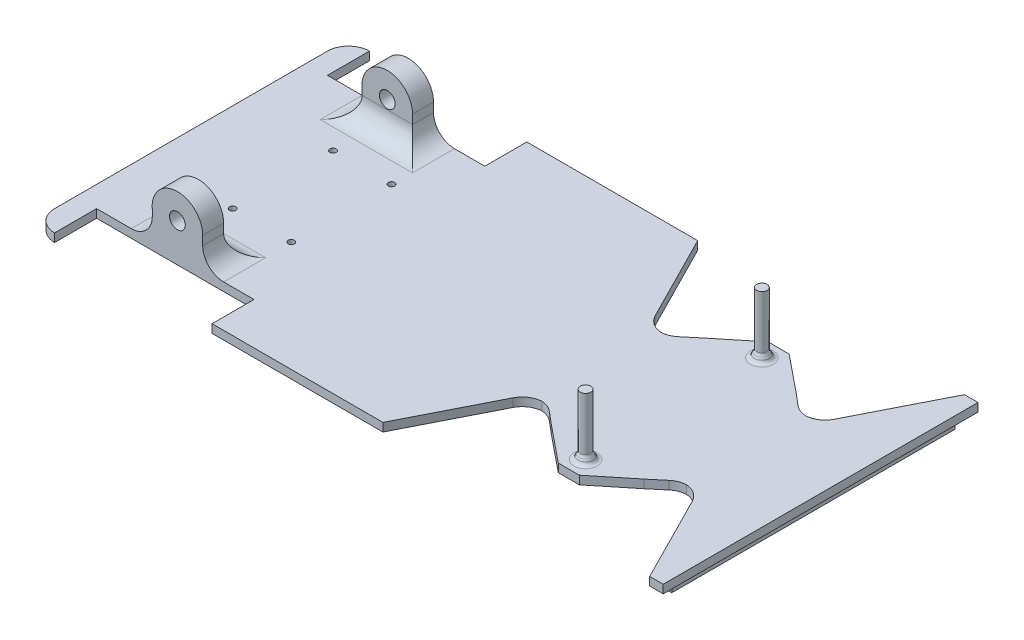
SolidWorks part; units mm, degrees
ref_plane "Front Plane" through (0, 0, 0) normal (0, 0, 1) x (1, 0, 0)
ref_plane "Top Plane" through (0, 0, 0) normal (0, 1, 0) x (1, 0, 0)
ref_plane "Right Plane" through (0, 0, 0) normal (1, 0, 0) x (0, 0, -1)
sketch "Sketch1" plane through (0, 0, 0) normal (0, 1, 0) x (1, 0, 0)
  line L0 (70, 75) -> (150, 75)
  line L1 (-140, 75) -> (70, 75)
  line L2 (-150, 65) -> (-150, -65)
  line L3 (-140, -75) -> (70, -75)
  line L4 (150, 65) -> (150, -30)
  line L5 (-150, 75) -> (150, -75) construction
  line L6 (-150, -75) -> (150, 75) construction
  line L7 (150, 75) -> (150, 65)
  line L8 (150, -30) -> (150, -75)
  line L9 (150, -75) -> (70, -75)
  arc A0 (-150, -65) -> (-140, -75) centre (-140, -65) ccw
  arc A1 (-140, 75) -> (-150, 65) centre (-140, 65) ccw
  point P0 (0, 0)
  dimension "D3" = 10
  dimension "D1" = 300
  dimension "D2" = 150
extrude "Boss-Extrude1" add sketch "Sketch1" along normal blind 4
sketch "Croquis3" plane through (0, 4, 0) normal (0, 1, 0) x (1, 0, 0)
  line L0 (-140, 75) -> (-140, -75) construction
  line L1 (150, 75) -> (-140, 75) construction
  line L2 (-140, 75) -> (-65, 75)
  line L3 (-140, 75) -> (-140, 55)
  line L4 (-140, 55) -> (-65, 55)
  line L5 (-65, 75) -> (-65, 55)
  line L6 (16.4398, 75) -> (143.5602, 75)
  line L10 (0, 0) -> (162.4285, 0) construction
  line L13 (-65, -75) -> (-65, -55)
  line L14 (-140, -55) -> (-65, -55)
  line L18 (-140, -55) -> (-140, -75)
  line L19 (-140, -75) -> (-65, -75)
  line L20 (80, 50) -> (80, -7.1915) construction
  line L21 (16.4398, 75) -> (47.926, 36.159)
  line L22 (47.926, 36.159) -> (57.926, 36.159)
  line L23 (57.926, 36.159) -> (75, 50)
  line L24 (85, 50) -> (75, 50)
  line L25 (102.074, 36.159) -> (85, 50)
  line L26 (112.074, 36.159) -> (102.074, 36.159)
  line L27 (143.5602, 75) -> (112.074, 36.159)
  line L28 (16.4398, -75) -> (143.5602, -75)
  line L29 (143.5602, -75) -> (112.074, -36.159)
  line L30 (112.074, -36.159) -> (102.074, -36.159)
  line L31 (102.074, -36.159) -> (85, -50)
  line L32 (85, -50) -> (75, -50)
  line L33 (57.926, -36.159) -> (75, -50)
  line L34 (47.926, -36.159) -> (57.926, -36.159)
  line L35 (16.4398, -75) -> (47.926, -36.159)
  point P34 (80, 50)
  line M10 (-140, -75) -> (150, -75)
  line M12 (150, 75) -> (-140, 75)
  dimension "D1" = 10
  dimension "D3" = 75
  dimension "D4" = 20
  dimension "D5" = 80
  dimension "D6" = 50
  dimension "D7" = 90
  dimension "D8" = 10
  dimension "D9" = 50
  dimension "D10" = 60
extrude "Cortar-Extruir1" cut sketch "Croquis3" against normal blind 10 contours L5 L3 L4 M12 | L14 L18 L13 M10 | L35 L29 L30 L31 L32 L33 L34 M10 | L27 L21 L22 L23 L24 L25 L26 M12 region at (80, 4, -59.5157) region at (-102.5, 4, -65) region at (-102.5, 4, 65) region at (80, 4, 59.5157)
sketch "Croquis4" plane through (0, 4, 0) normal (0, 1, 0) x (1, 0, 0)
  line L0 (0, 0) -> (112.4262, 0) construction
  line L1 (80, 50) -> (80, 42) construction
  line L2 (85, 50) -> (75, 50) construction
  circle A0 centre (80, 42) radius 3.5
  circle A1 centre (80, -42) radius 3.5
  dimension "D2" = 7
  dimension "D1" = 8
extrude "Saliente-Extruir1" add sketch "Croquis4" along normal blind 2
sketch "Croquis5" plane through (0, 6, 0) normal (0, 1, 0) x (1, 0, 0)
  line L0 (0, 0) -> (114.7473, 0) construction
  circle A0 centre (80, 42) radius 2.5
  circle A1 centre (80, -42) radius 2.5
  dimension "D1" = 5
extrude "Saliente-Extruir2" add sketch "Croquis5" along normal blind 27
sketch "Croquis7" plane through (0, 4, 0) normal (0, 1, 0) x (1, 0, 0)
  line L0 (57.926, 36.159) -> (48.6621, 28.3858)
  line L1 (48.6621, 28.3858) -> (40.0743, 28.3858)
  line L2 (40.0743, 28.3858) -> (16.4398, 75)
  line L3 (16.4398, 75) -> (57.926, 36.159)
  line L4 (0, 0) -> (77.7375, 0) construction
  line L5 (16.4398, -75) -> (57.926, -36.159)
  line L6 (85, 50) -> (75, 50) construction
  line L7 (80, 50) -> (80, 0) construction
  line L8 (80, 0) -> (77.0016, 0) construction
  line L9 (40.0743, -28.3858) -> (16.4398, -75)
  line L10 (48.6621, -28.3858) -> (40.0743, -28.3858)
  line L11 (57.926, -36.159) -> (48.6621, -28.3858)
  line L12 (143.5602, 75) -> (102.074, 36.159)
  line L13 (119.9257, 28.3858) -> (143.5602, 75)
  line L14 (111.3379, 28.3858) -> (119.9257, 28.3858)
  line L15 (102.074, 36.159) -> (111.3379, 28.3858)
  line L16 (102.074, -36.159) -> (111.3379, -28.3858)
  line L17 (111.3379, -28.3858) -> (119.9257, -28.3858)
  line L18 (119.9257, -28.3858) -> (143.5602, -75)
  line L19 (143.5602, -75) -> (102.074, -36.159)
  dimension "D1" = 20
  dimension "D2" = 140
  dimension "D3" = 8.5878
extrude "Cortar-Extruir3" cut sketch "Croquis7" against normal through all
fillet "Redondeo2" radius 2 1 edges at (80, 4, -38.5)
fillet "Redondeo3" radius 2 1 edges at (80, 6, -39.5)
fillet "Redondeo4" radius 2 1 edges at (80, 6, -38.5)
fillet "Redondeo5" radius 2 2 edges at (80, 4, 38.5) (80, 6, 39.5)
fillet "Redondeo6" radius 2 1 edges at (80, 6, 38.5)
fillet "Redondeo7" radius 10 8 edges at (40.0743, 2, 28.3858) (48.6621, 2, 28.3858) (40.0743, 2, -28.3858) (48.6621, 2, -28.3858) (111.3379, 2, -28.3858) (119.9257, 2, -28.3858) (111.3379, 2, 28.3858) (119.9257, 2, 28.3858)
sketch "Croquis9" plane through (0, 4, 0) normal (0, 1, 0) x (1, 0, 0)
  line L0 (-102.5, 55) -> (-102.5, -58.7003) construction
  line L1 (-140, 55) -> (-65, 55) construction
  line L2 (0, 0) -> (-147.9117, 0) construction
  line L3 (-107.59, 0) -> (-107.59, 25.23) construction
  line L4 (-107.59, 0) -> (-107.59, -22.57)
  line L5 (-79.79, 0) -> (-79.79, -22.45)
  line L6 (-79.79, 0) -> (-79.79, 25.33)
  circle A0 centre (-107.59, 25.23) radius 1.5
  circle A1 centre (-79.79, 25.33) radius 1.5
  circle A2 centre (-79.79, -22.45) radius 1.5
  circle A3 centre (-107.59, -22.57) radius 1.5
  dimension "D7" = 3
  dimension "D8" = 3
  dimension "D9" = 3
  dimension "D10" = 3
  dimension "D1" = 25.23
  dimension "D2" = 5.09
  dimension "D3" = 22.57
  dimension "D4" = 22.45
  dimension "D5" = 25.33
  dimension "D6" = 27.8
extrude "Cortar-Extruir4" cut sketch "Croquis9" against normal through all contours A3 | A2 | A0 | A1 region at (-78.7593, 4, 21.4193) region at (-80.8207, 4, -26.3607) region at (-107.59, 4, -25.23) region at (-108.6207, 4, 23.6007)
sketch "Croquis13" plane through (0, 0, -55) normal (0, 0, -1) x (-1, 0, 0)
  line L0 (102.496, 4) -> (102.496, 18.25) construction
  line L1 (0, 4) -> (147.9117, 4) construction
  circle A0 centre (102.496, 18.25) radius 3.75
  dimension "D2" = 7.5
  dimension "D1" = 14.25
sketch "Croquis14" plane through (0, 4, 0) normal (0, 1, 0) x (1, 0, 0)
  line L0 (-140, 55) -> (-65, 55) construction
  line L1 (-114.5, 55) -> (-90.5, 55)
  line L2 (-114.5, 55) -> (-114.5, 45)
  line L3 (-114.5, 45) -> (-90.5, 45)
  line L4 (-90.5, 55) -> (-90.5, 45)
  line L5 (-102.5, 55) -> (-102.5, -58.7003) construction
  dimension "D1" = 12
  dimension "D2" = 12
  dimension "D3" = 24
  dimension "D4" = 10
sketch "Croquis15" plane through (0, 0, -55) normal (0, 0, -1) x (-1, 0, 0)
  line L0 (89.4597, 4) -> (89.4597, 18.25)
  line L1 (0, 4) -> (147.9117, 4) construction
  line L2 (113.4597, 16.8589) -> (113.4597, 4)
  line L3 (113.4597, 4) -> (89.4597, 4)
  arc A0 (89.4597, 18.25) -> (113.4597, 16.8589) centre (101.5, 18.25) cw
  circle A1 centre (101.5, 18.25) radius 3.75
  line M6 (140, 4) -> (65, 4)
  dimension "D3" = 12.0403
  dimension "D4" = 7.5
  dimension "D1" = 24
  dimension "D2" = 36.5
extrude "Saliente-Extruir3" add sketch "Croquis15" against normal blind 10 contours A0 L0 L2 M6 region at (-89.8162, 11.125, -55)
fillet "Redondeo8" radius 10 3 edges at (-101.4597, 4, -45) (-89.4597, 4, -50) (-113.4597, 4, -50)
mirror "Simetría2" about plane through (0, 0, 0) normal (0, 0, 1) of "Cortar-Extruir1", "Redondeo8", "Saliente-Extruir3"
sketch "Croquis16" plane through (0, 0, 0) normal (0, -1, 0) x (1, 0, 0)
  line L0 (-94.1317, 47.5) -> (-94.1317, 14)
  line L1 (-144, 47.5) -> (-140, 47.5)
  line L2 (-144, 47.5) -> (-144, -47.5)
  line L3 (-144, -47.5) -> (-140, -47.5)
  line L4 (-140, 47.5) -> (-140, 14)
  line L5 (-140, 14) -> (-94.1317, 14)
  line L7 (-140, 10) -> (-94.1317, 10)
  line L9 (-140, -10) -> (-94.1317, -10)
  line L11 (-140, -14) -> (-94.1317, -14)
  line L13 (-90.1317, 47.5) -> (-90.1317, 14)
  line L14 (-44.2635, 47.5) -> (-44.2635, 14)
  line L15 (-40.2635, 47.5) -> (-40.2635, 14)
  line L16 (5.6048, 47.5) -> (5.6048, 14)
  line L17 (9.6048, 47.5) -> (9.6048, 14)
  line L18 (76.6048, 22.5) -> (80.6048, 22.5)
  line L19 (40.6048, 22.5) -> (44.6048, 22.5)
  line L20 (40.6048, 22.5) -> (40.6048, 14)
  line L21 (40.6048, -22.5) -> (44.6048, -22.5)
  line L22 (44.6048, 22.5) -> (44.6048, 14)
  line L23 (76.6048, 22.5) -> (76.6048, 14)
  line L24 (80.6048, 22.5) -> (80.6048, 14)
  line L25 (112.6048, 22.5) -> (116.6048, 22.5)
  line L26 (112.6048, 22.5) -> (112.6048, 14)
  line L27 (116.6048, 22.5) -> (116.6048, 14)
  line L28 (146.5901, 14) -> (146.5901, 10)
  line L30 (142.5901, -14) -> (142.5901, -67.5)
  line L31 (142.5901, -67.5) -> (146.5901, -67.5)
  line L32 (146.5901, -14) -> (146.5901, -67.5)
  line L34 (142.5901, 14) -> (142.5901, 67.5)
  line L35 (142.5901, 67.5) -> (146.5901, 67.5)
  line L36 (146.5901, 14) -> (146.5901, 67.5)
  line L38 (142.5901, 10) -> (142.5901, -10)
  line L40 (146.5901, 10) -> (146.5901, -14)
  line L41 (40.6048, 10) -> (40.6048, -10)
  line L42 (44.6048, 10) -> (44.6048, -10)
  line L43 (76.6048, 10) -> (76.6048, -10)
  line L44 (80.6048, 10) -> (80.6048, -10)
  line L45 (112.6048, 10) -> (112.6048, -10)
  line L46 (116.6048, 10) -> (116.6048, -10)
  line L47 (116.6048, 14) -> (142.5901, 14)
  line L48 (116.6048, 10) -> (142.5901, 10)
  line L49 (80.6048, 14) -> (112.6048, 14)
  line L50 (80.6048, 10) -> (112.6048, 10)
  line L51 (44.6048, -10) -> (76.6048, -10)
  line L52 (44.6048, -14) -> (76.6048, -14)
  line L53 (40.6048, -14) -> (40.6048, -22.5)
  line L54 (44.6048, -14) -> (44.6048, -22.5)
  line L55 (76.6048, -14) -> (76.6048, -22.5)
  line L56 (80.6048, -14) -> (80.6048, -22.5)
  line L57 (112.6048, -14) -> (112.6048, -22.5)
  line L58 (116.6048, -14) -> (116.6048, -22.5)
  line L59 (5.6048, 10) -> (5.6048, -10)
  line L60 (9.6048, 10) -> (9.6048, -10)
  line L61 (9.6048, 14) -> (40.6048, 14)
  line L62 (9.6048, 10) -> (40.6048, 10)
  line L63 (9.6048, -10) -> (40.6048, -10)
  line L64 (9.6048, -14) -> (40.6048, -14)
  line L65 (5.6048, -14) -> (5.6048, -47.5)
  line L66 (9.6048, -14) -> (9.6048, -47.5)
  line L67 (-94.1317, -14) -> (-94.1317, -47.5)
  line L68 (-90.1317, -14) -> (-90.1317, -47.5)
  line L69 (-44.2635, -14) -> (-44.2635, -47.5)
  line L70 (-40.2635, -14) -> (-40.2635, -47.5)
  line L71 (-94.1317, 10) -> (-94.1317, -10)
  line L72 (-90.1317, 10) -> (-90.1317, -10)
  line L73 (-44.2635, 10) -> (-44.2635, -10)
  line L74 (-40.2635, 10) -> (-40.2635, -10)
  line L75 (-40.2635, 14) -> (5.6048, 14)
  line L76 (-40.2635, 10) -> (5.6048, 10)
  line L77 (-40.2635, -10) -> (5.6048, -10)
  line L78 (-40.2635, -14) -> (5.6048, -14)
  line L79 (-90.1317, 14) -> (-44.2635, 14)
  line L80 (-90.1317, 10) -> (-44.2635, 10)
  line L81 (-90.1317, -10) -> (-44.2635, -10)
  line L82 (-90.1317, -14) -> (-44.2635, -14)
  line L83 (-140, 10) -> (-140, -10)
  line L84 (-140, -14) -> (-140, -47.5)
  line L85 (-144, -47.5) -> (-140, -47.5)
  line L86 (-94.1317, -47.5) -> (-90.1317, -47.5)
  line L87 (-44.2635, -47.5) -> (-40.2635, -47.5)
  line L88 (5.6048, -47.5) -> (9.6048, -47.5)
  line L89 (5.6048, 47.5) -> (9.6048, 47.5)
  line L90 (-40.2635, 47.5) -> (-44.2635, 47.5)
  line L91 (-94.1317, 47.5) -> (-90.1317, 47.5)
  line L92 (44.6048, 14) -> (76.6048, 14)
  line L93 (44.6048, 10) -> (76.6048, 10)
  line L94 (76.6048, -22.5) -> (80.6048, -22.5)
  line L95 (112.6048, -22.5) -> (116.6048, -22.5)
  line L96 (80.6048, -14) -> (112.6048, -14)
  line L97 (116.6048, -14) -> (142.5901, -14)
  line L98 (116.6048, -10) -> (142.5901, -10)
  line L99 (80.6048, -10) -> (112.6048, -10)
  dimension "D1" = 4
  dimension "D2" = 95
  dimension "D3" = 20
  dimension "D4" = 4
  dimension "D5" = 4
  dimension "D6" = 10
  dimension "D7" = 140
  dimension "D8" = 33.5
  dimension "D9" = 4
  dimension "D10" = 4
  dimension "D11" = 45
  dimension "D12" = 8.5
  dimension "D13" = 8.5
  dimension "D14" = 35
  dimension "D15" = 40.6048
  dimension "D17" = 4
  dimension "D18" = 135
  dimension "D19" = 53.5
  dimension "D20" = 142.5901
  dimension "D21" = 14
  dimension "D22" = 14
  dimension "D23" = 47.5
  dimension "D24" = 33.5
  dimension "D25" = 33.5
  dimension "D26" = 33.5
  dimension "D27" = 33.5
  dimension "D28" = 33.5
  dimension "D29" = 76.6048
  dimension "D30" = 8.5
  dimension "D31" = 8.5
  dimension "D16" = 3
extrude "Saliente-Extruir5" add sketch "Croquis16" along normal blind 5 contours L58 L97 L30 L31 L32 L40 L28 L36 L35 L34 L47 L27 L25 L26 L49 L24 L18 L23 L92 L22 L19 L20 L61 L17 L89 L16 L75 L15 L90 L14 L79 L13 L91 L0 L5 L4 L1 L2 L3 L84 L11 L67 L86 L68 L82 L69 L87 L70 L78 L65 L88 region at (-92.1317, 0, 44.2958)
